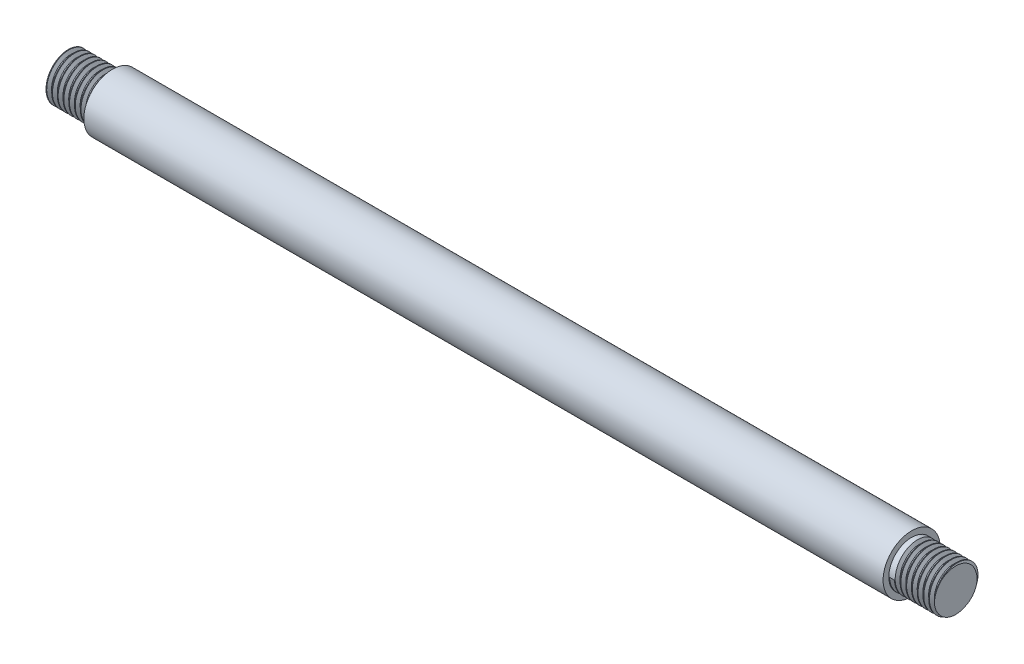
SolidWorks part; units mm, degrees
material "Commercial Bronze, UNS C22000 (90-10 Bronze)"
ref_plane "Front Plane" through (0, 0, 0) normal (0, 0, 1) x (1, 0, 0)
ref_plane "Top Plane" through (0, 0, 0) normal (0, 1, 0) x (1, 0, 0)
ref_plane "Right Plane" through (0, 0, 0) normal (1, 0, 0) x (0, 0, -1)
sketch "Sketch1" plane through (0, 0, 0) normal (1, 0, 0) x (0, 0, -1)
  circle A0 centre (0, 0) radius 5
  circle A1 centre (0, 0) radius 4
  dimension "D1" = 8
  dimension "D2" = 10
extrude "Boss-Extrude1" add sketch "Sketch1" along normal mid plane 156 contours A1 region at (0, 0, 0)
extrude "Boss-Extrude2" add sketch "Sketch1<3>" along normal mid plane 140
sketch "Sketch1<3>" plane through (0, 0, 0) normal (1, 0, 0) x (0, 0, -1) same geometry as "Sketch1"
thread "Thread1" pitch 1 method cut profile "Thread Profile1" start angle 0, offset 1, length 8, pitch 1, diameter 8
ref_plane "Plane1" through (79, 0, 4) normal (0, -1, 0) x (0, 0, 1)
sketch "Thread Profile1" plane through (79, 0, 4) normal (0, -1, 0) x (0, 0, 1)
  line L0 (0, 0) -> (0, 1) construction
  line L11 (0, 0) -> (0, 0.875)
  line L12 (0, 0.875) -> (-0.5413, 0.5625)
  line L13 (-0.5413, 0.5625) -> (-0.5413, 0.3125)
  line L15 (-0.5413, 0.3125) -> (0, 0)
  line L17 (-0.5413, 0.4375) -> (0, 0.4375) construction
  point P2 (0, 0)
  dimension "Pitch" = 1
  dimension "Profile_Angle" = 60
  dimension "Profile_Land" = 0.25
  dimension "Profile_Height" = 0.5413
thread "Thread2" pitch 1 method cut profile "Thread Profile2" start angle 0, offset 1, length 8, pitch 1, diameter 8
ref_plane "Plane2" through (-79, 0, -4) normal (0, -1, 0) x (0, 0, -1)
sketch "Thread Profile2" plane through (-79, 0, -4) normal (0, -1, 0) x (0, 0, -1)
  line L0 (0, 0) -> (0, 1) construction
  line L11 (0, 0) -> (0, 0.875)
  line L12 (0, 0.875) -> (-0.5413, 0.5625)
  line L13 (-0.5413, 0.5625) -> (-0.5413, 0.3125)
  line L15 (-0.5413, 0.3125) -> (0, 0)
  line L17 (-0.5413, 0.4375) -> (0, 0.4375) construction
  point P2 (0, 0)
  dimension "Pitch" = 1
  dimension "Profile_Angle" = 60
  dimension "Profile_Land" = 0.25
  dimension "Profile_Height" = 0.5413
